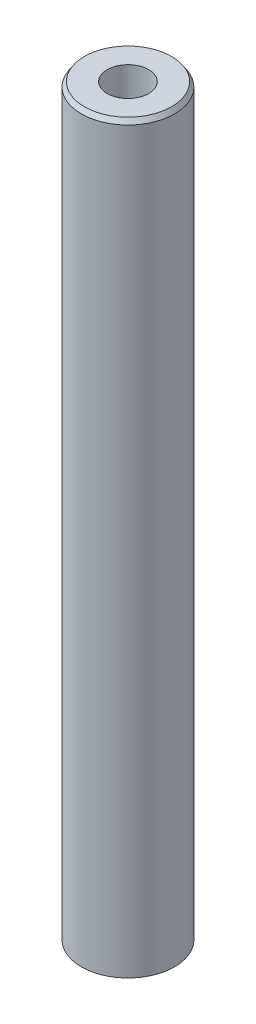
SolidWorks part; units mm, degrees
ref_plane "Front Plane" through (0, 0, 0) normal (0, 0, 1) x (1, 0, 0)
ref_plane "Top Plane" through (0, 0, 0) normal (0, 1, 0) x (1, 0, 0)
ref_plane "Right Plane" through (0, 0, 0) normal (1, 0, 0) x (0, 0, -1)
sketch "Sketch1" plane through (0, 0, 0) normal (0, 1, 0) x (1, 0, 0)
  circle A0 centre (0, 0) radius 37.5
  dimension "SHAFT_OD" = 75
extrude "Boss-Extrude1" add sketch "Sketch1" along normal blind 600
sketch "Sketch2" plane through (0, 0, 0) normal (0, 1, 0) x (1, 0, 0)
  circle A0 centre (0, 0) radius 16.6763
  dimension "BORE_D" = 33.3526
extrude "Cut-Extrude1" cut sketch "Sketch2" along normal through all
chamfer "Chamfer1" distance 3.755 angle 33.188 2 edges at (0, 600, 37.5) (0, 0, 37.5) first distance on face at (0, 600, 37.5) first distance on face at (0, 0, 16.6763)
